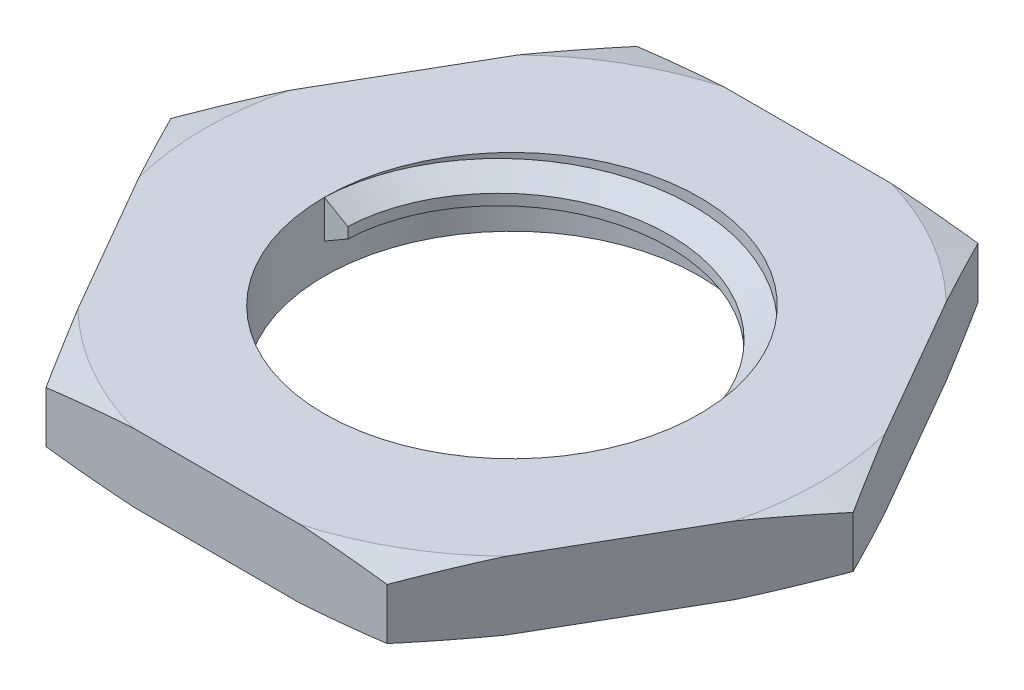
SolidWorks part; units mm, degrees
ref_plane "Alzado" through (0, 0, 0) normal (0, 0, 1) x (1, 0, 0)
ref_plane "Planta" through (0, 0, 0) normal (0, 1, 0) x (1, 0, 0)
ref_plane "Vista lateral" through (0, 0, 0) normal (1, 0, 0) x (0, 0, -1)
sketch "Croquis1" plane through (0, 0, 0) normal (0, 1, 0) x (1, 0, 0)
  line L1 (5, -8.6603) -> (10, 0)
  line L2 (10, 0) -> (5, 8.6603)
  line L3 (5, 8.6603) -> (-5, 8.6603)
  line L4 (-5, 8.6603) -> (-10, 0)
  line L5 (-10, 0) -> (-5, -8.6603)
  line L6 (-5, -8.6603) -> (5, -8.6603)
  circle A0 centre (0, 0) radius 8.6603 construction
  point P1 (0, 0)
  point P10 (0, 0)
  point P11 (9.8836, 0.2572)
extrude "Saliente-Extruir1" add sketch "Croquis1" along normal blind 2
sketch "Croquis2" plane through (0, 2, 0) normal (0, 1, 0) x (1, 0, 0)
  circle A0 centre (0, 0) radius 5.5
  dimension "D1" = 11
extrude "Cortar-Extruir1" cut sketch "Croquis2" against normal through all
thread "Rosca1" pitch 1.27 method extrude profile "Perfil de rosca1" start angle 0, offset 0, length 0, pitch 1.27, diameter 11
ref_plane "Plano1" through (-5.5, 2, 0) normal (0, 0, 1) x (-1, 0, 0)
sketch "Perfil de rosca1" plane through (-5.5, 2, 0) normal (0, 0, 1) x (-1, 0, 0)
  line L0 (0, 0) -> (0, 1.27) construction
  line L11 (0, 0) -> (0, 1.1112)
  line L12 (0, 1.1112) -> (-0.6874, 0.7144)
  line L13 (-0.6874, 0.7144) -> (-0.6874, 0.3969)
  line L15 (-0.6874, 0.3969) -> (0, 0)
  line L17 (-0.6874, 0.5556) -> (0, 0.5556) construction
  point P2 (0, 0)
  dimension "Pitch" = 1.27
  dimension "Profile_Angle" = 60
  dimension "Profile_Land" = 0.3175
  dimension "Profile_Height" = 0.6874
sketch "Croquis5" plane through (0, 0, 0) normal (0, 0, 1) x (1, 0, 0)
  line L0 (10, 2) -> (9, 2)
  line L1 (10, 2) -> (5, 2) construction
  line L2 (9, 2) -> (10, 1.75)
  line L3 (10, 2) -> (10, 0) construction
  line L4 (10, 1.75) -> (10, 2)
  line L5 (10, 0) -> (9, 0)
  line L6 (10, 0) -> (5, 0) construction
  line L7 (9, 0) -> (10, 0.25)
  line L8 (10, 0.25) -> (10, 0)
  line L9 (0, 2) -> (0, 0) construction
  line L11 (5, 2) -> (-5, 2) construction
  dimension "D1" = 1
  dimension "D2" = 0.25
revolve "Cortar-Revolución2" cut sketch "Croquis5" angle 360 about L9
